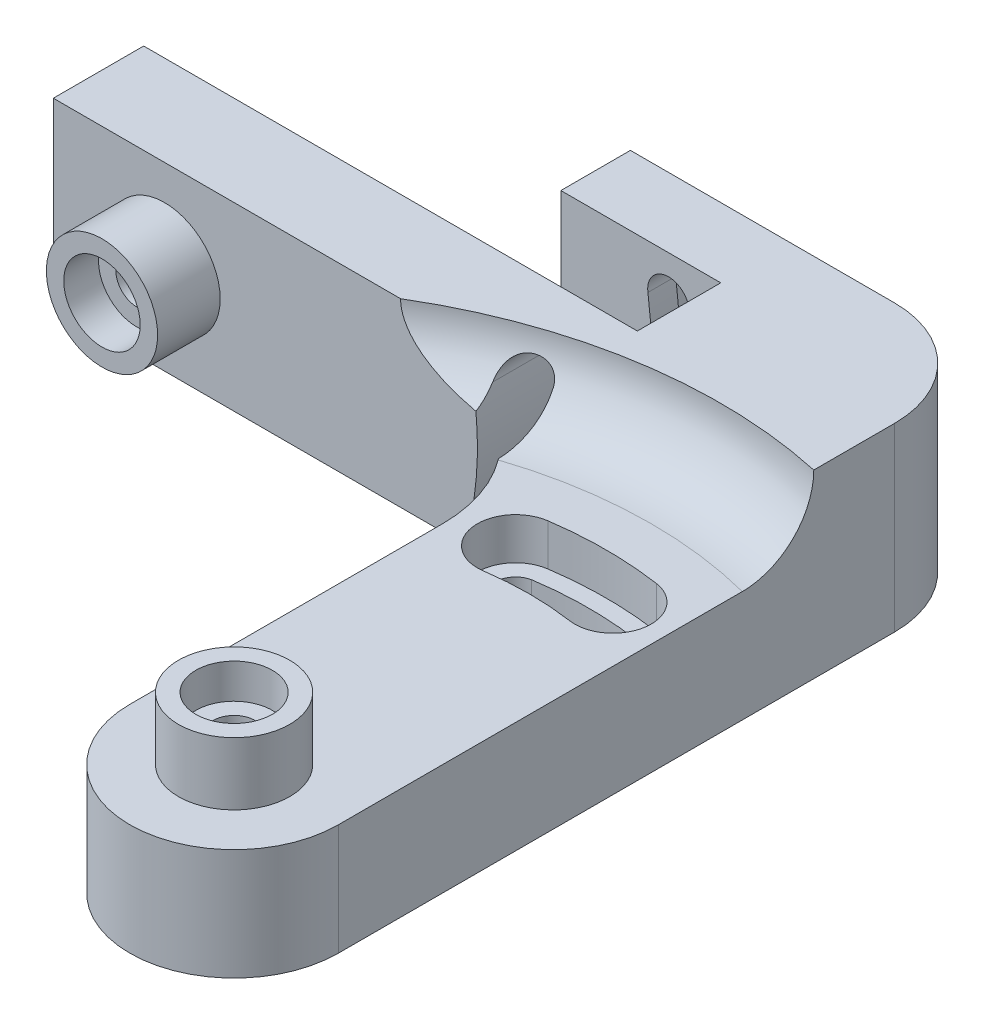
SolidWorks part; units mm, degrees
note: The reader was unsure of these and kept them because the rebuilt part matched: shared geometry of "Sketch6<8>".
ref_plane "Front Plane" through (0, 0, 0) normal (0, 0, 1) x (1, 0, 0)
ref_plane "Top Plane" through (0, 0, 0) normal (0, 1, 0) x (1, 0, 0)
ref_plane "Right Plane" through (0, 0, 0) normal (1, 0, 0) x (0, 0, -1)
sketch "Sketch1" plane through (0, 0, 0) normal (0, 1, 0) x (1, 0, 0)
  line L0 (0, 0) -> (0, 24) construction
  line L1 (0, -7.5) -> (0, 49000) construction
  line L2 (-7.5, 36.5) -> (-43, 36.5)
  line L3 (-43, 36.5) -> (-43, 32.5)
  line L5 (7.5, 0) -> (7.5, 40)
  line L6 (0, 47.5) -> (-19, 47.5)
  line L7 (-19, 47.5) -> (-19, 42.5)
  line L8 (-19, 42.5) -> (-7.5, 42.5)
  line L9 (-43, 32.5) -> (-17.5, 32.5)
  line L11 (-7.5, 36.5) -> (-7.5, 42.5)
  line L12 (-7.5, 0) -> (-7.5, 22.5)
  circle A1 centre (0, 0) radius 1.5
  arc A3 (3.5, 23.7434) -> (-3.5, 23.7434) centre (0, 0) ccw construction
  arc A4 (-3.8223, 25.2084) -> (-3.2806, 22.2596) centre (-3.5, 23.7434) ccw
  arc A5 (3.1485, 22.2786) -> (3.8936, 25.1975) centre (3.5, 23.7434) ccw
  arc A7 (3.8936, 25.1975) -> (-3.8223, 25.2084) centre (0, 0) ccw
  arc A8 (3.1485, 22.2786) -> (-3.2806, 22.2596) centre (0, 0) ccw
  arc A9 (7.5, 40) -> (0, 47.5) centre (0, 40) ccw
  arc A16 (-7.5, 0) -> (7.5, 0) centre (0, 0) ccw
  arc A17 (-7.5, 22.5) -> (-17.5, 32.5) centre (-17.5, 22.5) ccw
  dimension "D3" = 3
  dimension "D6" = 3
  dimension "D7" = 40
  dimension "D8" = 15
  dimension "D10" = 6
  dimension "D11" = 10
  dimension "D2" = 24
  dimension "D4" = 3.5
  dimension "D5" = 3.5
  dimension "D9" = 5
  dimension "D13" = 26.5
  dimension "D14" = 50.5
  dimension "D15" = 4
  dimension "D17" = 7.5
extrude "Boss-Extrude1" add sketch "Sketch1" along normal blind 8
sketch "Sketch2" plane through (0, 8, 0) normal (0, 1, 0) x (1, 0, 0)
  circle A0 centre (0, 0) radius 4
  circle A2 centre (0, 0) radius 1.5
  dimension "D1" = 8
  dimension "D2" = 3
extrude "Boss-Extrude2" add sketch "Sketch2" along normal blind 2
sketch "Sketch4" plane through (0, 10, 0) normal (0, 1, 0) x (1, 0, 0)
  circle A0 centre (0, 0) radius 4
  circle A1 centre (0, 0) radius 2.75
  dimension "D1" = 5.5
  dimension "D2" = 8
extrude "Boss-Extrude3" add sketch "Sketch4" along normal blind 2.5
sketch "Sketch5" plane through (0, 8, 0) normal (0, 1, 0) x (1, 0, 0)
  arc A0 (-3.901, 26.464) -> (-3.099, 21.0228) centre (-3.5, 23.7434) ccw
  arc A1 (3.099, 21.0228) -> (3.901, 26.464) centre (3.5, 23.7434) ccw
  arc A2 (3.901, 26.464) -> (-3.901, 26.464) centre (0, 0) ccw
  arc A3 (3.099, 21.0228) -> (-3.099, 21.0228) centre (0, 0) ccw
  dimension "D1" = 5.5
  dimension "D2" = 5.5
extrude "Cut-Extrude1" cut sketch "Sketch5" against normal blind 3
sketch "Sketch11" plane through (0, 8, 0) normal (0, 1, 0) x (1, 0, 0)
  line L0 (-7.5, 42.5) -> (-19, 42.5)
  line L3 (0, 47.5) -> (-19, 47.5)
  line L4 (-19, 47.5) -> (-19, 42.5)
  line L14 (-19, 42.5) -> (-7.5, 42.5)
  line L15 (-7.5, 42.5) -> (-7.5, 36.5)
  line L16 (-7.5, 36.5) -> (-43, 36.5)
  line L17 (-43, 36.5) -> (-43, 32.5)
  line L18 (-43, 32.5) -> (-17.5, 32.5)
  line L19 (-7.5, 22.5) -> (-7.5, 0)
  line L20 (7.5, 0) -> (7.5, 40)
  line L21 (0, 47.5) -> (-19, 47.5)
  line L26 (-7.5, 42.5) -> (-7.5, 36.5)
  line L27 (-7.5, 36.5) -> (-43, 36.5)
  line L28 (-43, 36.5) -> (-43, 32.5)
  line L29 (-43, 32.5) -> (-17.5, 32.5)
  line L30 (-7.5, 22.5) -> (-7.5, 0)
  line L31 (7.5, 0) -> (7.5, 40)
  line L34 (-19, 47.5) -> (-19, 42.5)
  arc A0 (7.5, 34.187) -> (-14.2635, 31.9618) centre (0, 0) ccw
  arc A3 (-7.5, 22.5) -> (-17.5, 32.5) centre (-17.5, 22.5) ccw
  arc A4 (-7.5, 0) -> (7.5, 0) centre (0, 0) ccw
  arc A5 (7.5, 40) -> (0, 47.5) centre (0, 40) ccw
  arc A6 (-7.5, 22.5) -> (-17.5, 32.5) centre (-17.5, 22.5) ccw
  arc A7 (-7.5, 0) -> (7.5, 0) centre (0, 0) ccw
  arc A8 (7.5, 40) -> (0, 47.5) centre (0, 40) ccw
  dimension "D2" = 35
  dimension "D1" = 0
extrude "Boss-Extrude4" add sketch "Sketch11" along normal blind 5
sketch "Sketch12" plane through (0, 0, -32.5) normal (0, 0, 1) x (1, 0, 0)
  line L8 (-43, 0) -> (-17.5, 0)
  line L9 (-17.5, 0) -> (-17.5, 13)
  line L10 (-17.5, 13) -> (-43, 13)
  line L11 (-43, 13) -> (-43, 0)
  line L12 (-43, 0) -> (-17.5, 0)
  line L13 (-17.5, 0) -> (-17.5, 13)
  line L14 (-17.5, 13) -> (-43, 13)
  line L15 (-43, 13) -> (-43, 0)
  dimension "D1" = 0
extrude "Boss-Extrude5" add sketch "Sketch12" along normal blind 2.5
sketch "Sketch14" plane through (0, 0, 0) normal (0, 1, 0) x (1, 0, 0)
  line L0 (-17.5, 30.3109) -> (-17.5, 32.5)
  arc A0 (-14.2635, 31.9618) -> (-17.5, 30.3109) centre (0, 0) ccw
  arc A1 (-14.2635, 31.9618) -> (-17.5, 32.5) centre (-17.5, 22.5) ccw construction
  arc A2 (-14.2635, 31.9618) -> (-17.5, 32.5) centre (-17.5, 22.5) ccw
extrude "Boss-Extrude6" add sketch "Sketch14" along normal up to surface (13 mm away) up to face at (-14.3222, 13, -37.9233)
sketch "Sketch15" plane through (0, 0, 0) normal (0, 1, 0) x (1, 0, 0)
  line L0 (-17.5, 30) -> (-17.5, 30.3109) construction
  line L1 (-17.5, 30) -> (-17.5, 30.3109)
  line L2 (-17.5, 30) -> (-10.8856, 30)
  arc A0 (-7.5, 22.5) -> (-14.2635, 31.9618) centre (-17.5, 22.5) ccw construction
  arc A1 (-10.8856, 30) -> (-14.2635, 31.9618) centre (-17.5, 22.5) ccw
  arc A2 (7.5, 34.187) -> (-17.5, 30.3109) centre (0, 0) ccw construction
  arc A3 (-14.2635, 31.9618) -> (-17.5, 30.3109) centre (0, 0) ccw
extrude "Boss-Extrude7" add sketch "Sketch15" along normal up to surface (8 mm away) up to face at (-2.585, 8, -16.7954)
sketch "Sketch16" plane through (0, 13, 0) normal (0, 1, 0) x (1, 0, 0)
  circle A0 centre (0, 0) radius 35
  circle A1 centre (0, 0) radius 33.5019
extrude "Cut-Extrude4" cut sketch "Sketch16" against normal up to surface (5 mm away) up to face at (-6.4916, 8, -20.3143)
fillet "Fillet2" radius 5 1 edges at (-5.6649, 8, -34.5385)
sketch "Sketch6" plane through (0, 0, -47.5) normal (0, 0, -1) x (-1, 0, 0)
  line L0 (7.5, 0) -> (43, 0) construction
  line L1 (43, 13) -> (43, 0) construction
  line L2 (35, 6.5) -> (-18.8, 6.5) construction
  line L3 (35, -993.5) -> (35, 49006.5) construction
  circle A0 centre (35, 6.5) radius 1.5
  circle A1 centre (11, 6.5) radius 1.5 construction
  arc A3 (12.7405, 9.7812) -> (9.7726, 10.2188) centre (11.2566, 10) ccw
  arc A4 (9.7726, 2.7812) -> (12.7405, 3.2187) centre (11.2566, 3) ccw
  arc A8 (12.7405, 9.7812) -> (12.7405, 3.2187) centre (35, 6.5) ccw
  arc A9 (9.7726, 10.2188) -> (9.7726, 2.7812) centre (35, 6.5) ccw
  arc A14 (13.9772, 9.599) -> (8.536, 10.401) centre (11.2566, 10) ccw
  arc A18 (8.536, 10.401) -> (8.536, 2.599) centre (35, 6.5) ccw
  arc A19 (13.9772, 9.599) -> (13.9772, 3.401) centre (35, 6.5) ccw
  arc A20 (8.536, 2.599) -> (13.9772, 3.401) centre (11.2566, 3) ccw
  dimension "D1" = 3
  dimension "D4" = 3
  dimension "D8" = 3
  dimension "D9" = 3
  dimension "D10" = 25.5
  dimension "D11" = 5.5
  dimension "D12" = 22.5
  dimension "D13" = 2.75
  dimension "D2" = 6.5
  dimension "D3" = 24
  dimension "D5" = 8
  dimension "D6" = 3.5
  dimension "D7" = 3.5
extrude "Cut-Extrude5" cut sketch "Sketch6" against normal through all contours A3 A9 A4 A8 | A0
extrude "Cut-Extrude6" cut sketch "Sketch6<8>" against normal blind 3
sketch "Sketch6<8>" plane through (0, 0, -47.5) normal (0, 0, -1) x (-1, 0, 0) same geometry as "Sketch6"
sketch "Sketch17" plane through (0, 0, -30) normal (0, 0, 1) x (1, 0, 0)
  circle A0 centre (-35, 6.5) radius 4
  circle A1 centre (-35, 6.5) radius 1.5
  dimension "D1" = 8
  dimension "D2" = 3
extrude "Boss-Extrude8" add sketch "Sketch17" along normal blind 2
sketch "Sketch18" plane through (0, 0, -28) normal (0, 0, 1) x (1, 0, 0)
  circle A0 centre (-35, 6.5) radius 4
  circle A1 centre (-35, 6.5) radius 2.75
  dimension "D1" = 5.5
  dimension "D2" = 8
extrude "Boss-Extrude9" add sketch "Sketch18" along normal blind 2.5
